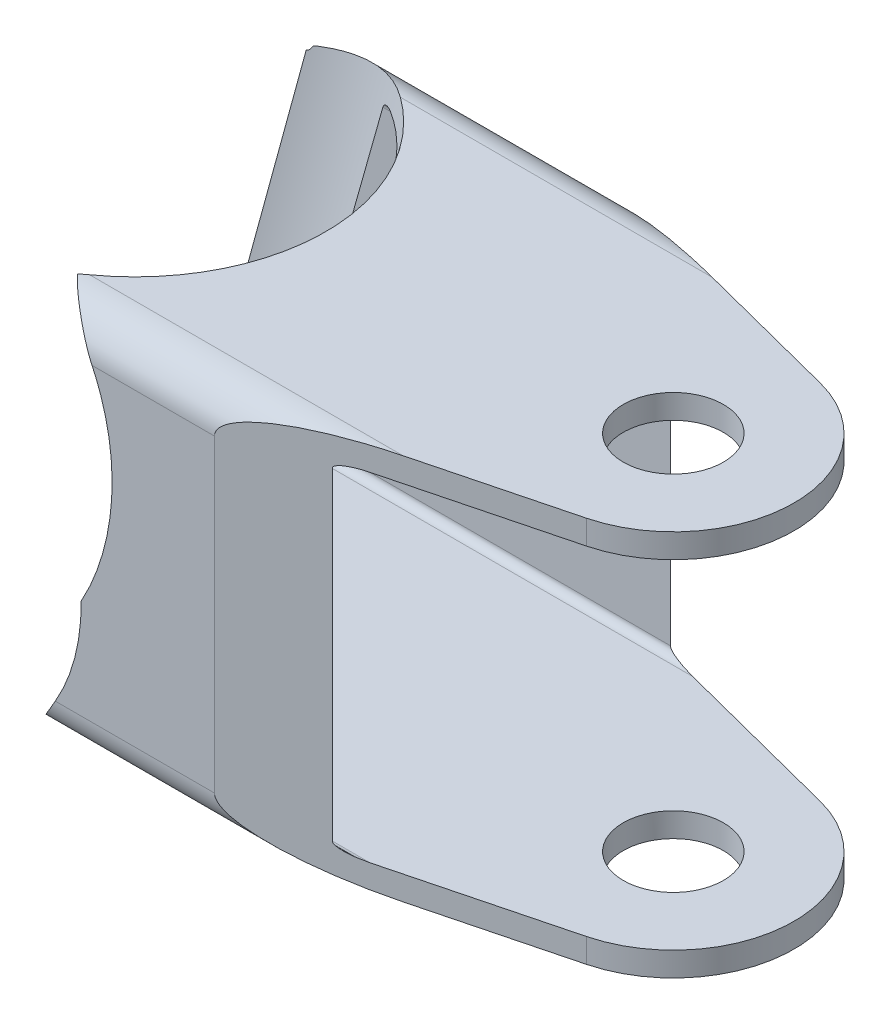
SolidWorks part; units mm, degrees
material "AISI 4130 Steel, annealed at 865C"
ref_plane "Front Plane" through (0, 0, 0) normal (0, 0, 1) x (1, 0, 0)
ref_plane "Top Plane" through (0, 0, 0) normal (0, 1, 0) x (1, 0, 0)
ref_plane "Right Plane" through (0, 0, 0) normal (1, 0, 0) x (0, 0, -1)
sketch "Sketch1" plane through (0, 0, 0) normal (1, 0, 0) x (0, 0, -1)
  line L1 (-10.16, 12.7) -> (10.16, 12.7)
  line L2 (-12.7, 10.16) -> (-12.7, -10.16)
  line L3 (-10.16, -12.7) -> (10.16, -12.7)
  line L4 (12.7, 10.16) -> (12.7, -10.16)
  arc A0 (-10.16, 12.7) -> (-12.7, 10.16) centre (-10.16, 10.16) ccw
  arc A1 (-10.16, -12.7) -> (-12.7, -10.16) centre (-10.16, -10.16) cw
  arc A2 (10.16, 12.7) -> (12.7, 10.16) centre (10.16, 10.16) cw
  arc A3 (12.7, -10.16) -> (10.16, -12.7) centre (10.16, -10.16) cw
  point P4 (0, -12.7)
  point P7 (0, 0)
  point P15 (12.7, 0)
  dimension "D3" = 2.54
  dimension "D4" = 2.54
  dimension "D5" = 2.54
  dimension "D6" = 2.54
  dimension "D1" = 25.4
  dimension "D2" = 20.32
extrude "Boss-Extrude1" add sketch "Sketch1" along normal blind 25.4 and the other way blind 34.925
sketch "Sketch11" plane through (25.4, 0, 0) normal (1, 0, 0) x (0, 0, -1)
  line L0 (-10.16, -12.7) -> (10.16, -12.7) construction
  line L1 (-10.6045, 11.1125) -> (10.6045, 11.1125)
  line L2 (-11.1125, 10.6045) -> (-11.1125, -10.6045)
  line L3 (-10.6045, -11.1125) -> (10.6045, -11.1125)
  line L4 (11.1125, 10.6045) -> (11.1125, -10.6045)
  line L5 (10.16, 12.7) -> (-10.16, 12.7) construction
  line L6 (12.7, -10.16) -> (12.7, 10.16) construction
  line L7 (-12.7, 10.16) -> (-12.7, -10.16) construction
  arc A0 (10.6045, 11.1125) -> (11.1125, 10.6045) centre (10.6045, 10.6045) cw
  arc A1 (10.6045, -11.1125) -> (11.1125, -10.6045) centre (10.6045, -10.6045) ccw
  arc A2 (-11.1125, -10.6045) -> (-10.6045, -11.1125) centre (-10.6045, -10.6045) ccw
  arc A3 (-10.6045, 11.1125) -> (-11.1125, 10.6045) centre (-10.6045, 10.6045) ccw
  dimension "D1" = 1.5875
  dimension "D2" = 1.5875
  dimension "D3" = 1.5875
  dimension "D4" = 1.5875
  dimension "D5" = 0.508
extrude "Cut-Extrude4" cut sketch "Sketch11" against normal through all
sketch "Sketch12" plane through (0, 12.7, 0) normal (0, 1, 0) x (1, 0, 0)
  line L1 (0, 12.7) -> (50.8, 12.7)
  line L2 (50.8, 12.7) -> (50.8, -12.7)
  line L12 (50.8, -12.7) -> (0, -12.7)
  line L13 (19.4444, -7.6861) -> (0, -12.7)
  line L14 (19.4444, 7.6861) -> (0, 12.7)
  line L15 (-34.925, -12.7) -> (25.4, -12.7) construction
  line L16 (-34.925, 12.7) -> (25.4, 12.7) construction
  line L18 (25.4, 10.16) -> (25.4, -10.16) construction
  arc A1 (19.4444, -7.6861) -> (19.4444, 7.6861) centre (17.4625, 0) ccw
  point P8 (18.1688, 9.2165)
  line M6 (-34.925, -10.16) -> (25.4, -10.16)
  line M7 (25.4, -10.16) -> (25.4, 10.16)
  line M8 (25.4, 10.16) -> (-34.925, 10.16)
  line M9 (-34.925, 10.16) -> (-34.925, -10.16)
  dimension "D2" = 50.8
  dimension "D1" = 17.4625
extrude "Cut-Extrude5" cut sketch "Sketch12" against normal through all contours M9 M8 M7 M6 | M7 M8 M9 | M6 M7 region at (34.888, 12.7, 0) region at (20.955, 12.7, -8.1283) region at (20.955, 12.7, 8.1283)
sketch "Sketch14" plane through (0, 12.7, 0) normal (0, 1, 0) x (1, 0, 0)
  circle A0 centre (17.4625, 0) radius 3.2893
  arc A2 (19.4444, -7.6861) -> (19.4444, 7.6861) centre (17.4625, 0) ccw construction
  point P0 (17.4625, 0)
  point P6 (25.4, 0)
  dimension "D2" = 6.5786
  dimension "D1" = 7.9375
  dimension "D3" = 17.4625
extrude "Cut-Extrude6" cut sketch "Sketch14" against normal through all
ref_axis "Axis1" through (-76.1607, 10.6803, 0.1041) along (0.9661, -0.2581, 0)
ref_axis "Axis2" through (-72.0904, 10.0753, 62.0547) along (0.6127, -0.1697, -0.7719)
ref_axis "Axis3" through (-14.5245, -5.1858, 76.9148) along (-0.1086, 0.0213, -0.9939)
ref_axis "Axis4" through (-5.7422, 30.6897, 69.6754) along (-0.2163, -0.431, -0.876)
ref_axis "Axis5" through (-6.826, 56.7068, -0.3649) along (-0.2581, -0.9661, 0.0075)
ref_point "Point1"
ref_point "Point2"
ref_point "Point3"
ref_point "Point4"
ref_point "Point5"
ref_plane "Plane1" through (-34.925, -0.3344, 0.1041) normal (0.9661, -0.2581, 0) x (0, 0, -1)
ref_plane "Plane2" through (-32.9168, -0.7728, 12.7) normal (0.6127, -0.1697, -0.7719) x (-0.7903, -0.1315, -0.5984)
ref_plane "Plane3" through (-21.5426, -3.811, 12.7) normal (-0.1086, 0.0213, -0.9939) x (-0.9941, -0.0023, 0.1086)
ref_plane "Plane4" through (-19.8094, 2.6562, 12.7) normal (-0.2163, -0.431, -0.876) x (-0.9763, 0.0955, 0.1941)
ref_plane "Plane5" through (-18.5809, 12.7, -0.0223) normal (-0.2581, -0.9661, 0.0075) x (-0.9661, 0.2581, -0.002)
sketch "Sketch16" plane through (-34.925, -0.3344, 0.1041) normal (0.9661, -0.2581, 0) x (0, 0, -1)
  circle A0 centre (0, 0) radius 12.7
sketch "Sketch17" plane through (-32.9168, -0.7728, 12.7) normal (0.6127, -0.1697, -0.7719) x (-0.7903, -0.1315, -0.5984)
  circle A0 centre (0, 0) radius 12.7
sketch "Sketch18" plane through (-21.5426, -3.811, 12.7) normal (-0.1086, 0.0213, -0.9939) x (-0.9941, -0.0023, 0.1086)
  circle A0 centre (0, 0) radius 12.7
sketch "Sketch19" plane through (-19.8094, 2.6562, 12.7) normal (-0.2163, -0.431, -0.876) x (-0.9763, 0.0955, 0.1941)
  circle A0 centre (0, 0) radius 12.7
sketch "Sketch20" plane through (-18.5809, 12.7, -0.0223) normal (-0.2581, -0.9661, 0.0075) x (-0.9661, 0.2581, -0.002)
  circle A0 centre (0, 0) radius 12.7
extrude "Cut-Extrude7" cut sketch "Sketch16" against normal blind 12.7 and the other way blind 11.43
extrude "Cut-Extrude9" cut sketch "Sketch17" against normal blind 12.7 and the other way blind 4.445
extrude "Cut-Extrude10" cut sketch "Sketch18" against normal blind 12.7 and the other way blind 11.684 body kept at (-30.0495, 11.5914, 12.2582)
extrude "Cut-Extrude11" cut sketch "Sketch19" against normal blind 12.7 and the other way blind 8.128
extrude "Cut-Extrude12" cut sketch "Sketch20" against normal blind 12.7 and the other way blind 35.814
ref_plane "Plane6" through (-20.5099, 5.4785, 0) normal (-0.9661, 0.2581, 0) x (-0.2581, -0.9661, 0.0075)
sketch "Sketch23" plane through (-20.5099, 5.4785, 0) normal (-0.9661, 0.2581, 0) x (-0.2581, -0.9661, 0.0075)
  line L1 (-18.212, 20.3882) -> (25.7273, 20.3882)
  line L2 (-18.212, 20.3882) -> (-18.212, -17.8782)
  line L3 (-18.212, -17.8782) -> (25.7273, -17.8782)
  line L4 (25.7273, 20.3882) -> (25.7273, -17.8782)
extrude "Cut-Extrude13" cut sketch "Sketch23" along normal through all
